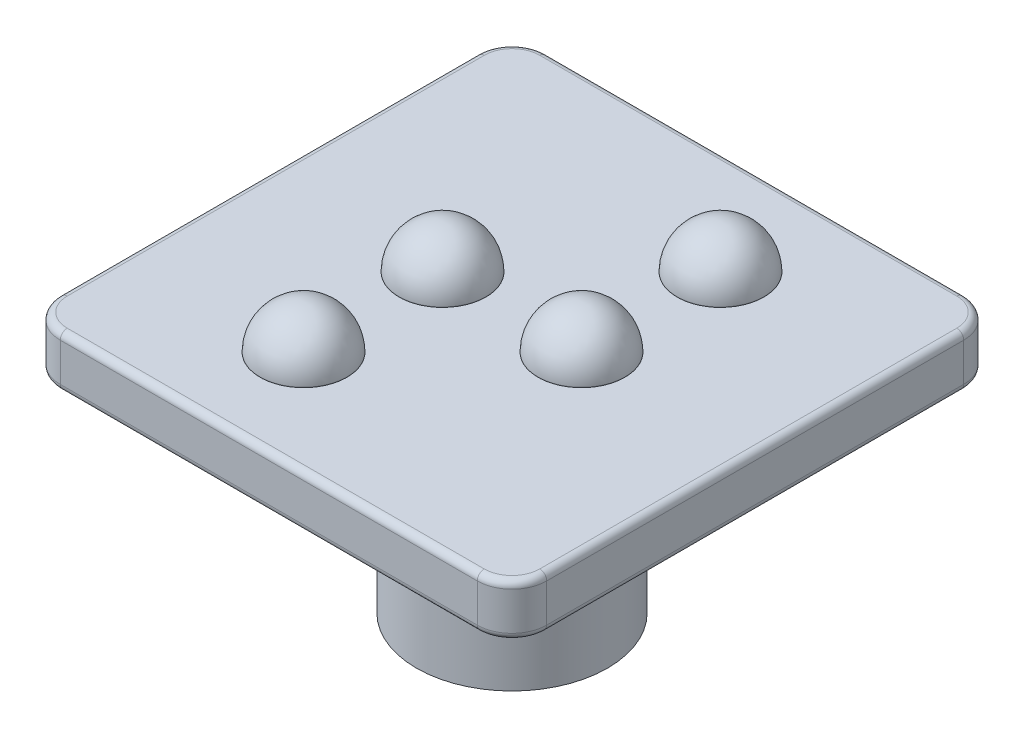
SolidWorks part; units mm, degrees
ref_plane "Front Plane" through (0, 0, 0) normal (0, 0, 1) x (1, 0, 0)
ref_plane "Top Plane" through (0, 0, 0) normal (0, 1, 0) x (1, 0, 0)
ref_plane "Right Plane" through (0, 0, 0) normal (1, 0, 0) x (0, 0, -1)
sketch "Sketch1" plane through (0, 0, 0) normal (0, 1, 0) x (1, 0, 0)
  line L1 (-7.3247, 4.3967) -> (4.6753, 4.3967)
  line L2 (-8.3247, 3.3967) -> (-8.3247, -8.6033)
  line L3 (-7.3247, -9.6033) -> (4.6753, -9.6033)
  line L4 (5.6753, 3.3967) -> (5.6753, -8.6033)
  arc A0 (-8.3247, -8.6033) -> (-7.3247, -9.6033) centre (-7.3247, -8.6033) ccw
  arc A1 (4.6753, -9.6033) -> (5.6753, -8.6033) centre (4.6753, -8.6033) ccw
  arc A2 (4.6753, 4.3967) -> (5.6753, 3.3967) centre (4.6753, 3.3967) cw
  arc A3 (-7.3247, 4.3967) -> (-8.3247, 3.3967) centre (-7.3247, 3.3967) ccw
  point P8 (5.6753, -9.6033)
  point P11 (5.6753, 4.3967)
  point P14 (-8.3247, 4.3967)
  dimension "D3" = 1
  dimension "D1" = 14
  dimension "D2" = 14
extrude "Boss-Extrude1" add sketch "Sketch1" along normal blind 1.5
sketch "Sketch2" plane through (0, 0, 0) normal (0, -1, 0) x (1, 0, 0)
  line L0 (-7.3247, 9.6033) -> (4.6753, 9.6033) construction
  line L1 (5.6753, 8.6033) -> (5.6753, -3.3967) construction
  line L2 (-1.3247, -4.3967) -> (-1.3247, 9.6033) construction
  line L3 (-8.3247, 2.6033) -> (5.6753, 2.6033) construction
  line L4 (-8.3247, -3.3967) -> (-8.3247, 8.6033) construction
  circle A0 centre (-1.3247, 2.6033) radius 2.75
  dimension "D1" = 7
  dimension "D2" = 7
extrude "Boss-Extrude2" add sketch "Sketch2" along normal blind 6
sketch "Sketch3" plane through (0, -6, 0) normal (0, -1, 0) x (1, 0, 0)
  line L0 (-1.3247, 5.3533) -> (-1.3247, -0.1467) construction
  line L1 (-3.3247, 3.1533) -> (0.6753, 3.1533)
  line L2 (-3.3247, 3.1533) -> (-3.3247, 2.0533)
  line L3 (-3.3247, 2.0533) -> (0.6753, 2.0533)
  line L4 (0.6753, 3.1533) -> (0.6753, 2.0533)
  line L5 (-1.8747, 4.6033) -> (-0.7747, 4.6033)
  line L6 (-1.8747, 4.6033) -> (-1.8747, 0.6033)
  line L7 (-1.8747, 0.6033) -> (-0.7747, 0.6033)
  line L8 (-0.7747, 4.6033) -> (-0.7747, 0.6033)
  line L9 (-4.0747, 2.6033) -> (1.4253, 2.6033) construction
  circle A3 centre (-1.3247, 2.6033) radius 2.75 construction
  circle A4 centre (-1.3247, 2.6033) radius 2.75 construction
  dimension "D7" = 0.55
  dimension "D1" = 4
  dimension "D2" = 1.1
  dimension "D3" = 1.1
  dimension "D4" = 4
  dimension "D8" = 0.55
extrude "Cut-Extrude1" cut sketch "Sketch3" against normal blind 6 contours L8 L5 L6 L1 | L1 L8 L3 L4 | L8 L1 L6 L3 | L6 L1 L2 L3 | L8 L3 L6 L7 region at (-2.5997, -6, 2.6033) region at (-1.3247, -6, 3.8783) region at (-1.3247, -6, 2.6033) region at (-0.0497, -6, 2.6033) region at (-1.3247, -6, 1.3283)
chamfer "Chamfer1" distance 0.3 angle 45 12 edges at (-1.3247, -6, 0.6033) (-1.8747, -6, 1.3283) (-2.5997, -6, 2.0533) (-3.3247, -6, 2.6033) (-2.5997, -6, 3.1533) (-0.7747, -6, 1.3283) (-0.0497, -6, 2.0533) (0.6753, -6, 2.6033) (-0.0497, -6, 3.1533) (-0.7747, -6, 3.8783) (-1.3247, -6, 4.6033) (-1.8747, -6, 3.8783)
fillet "Fillet1" radius 1 1 edges at (-1.3247, 0, -0.1467)
sketch "Sketch4" plane through (0, 1.5, 0) normal (0, 1, 0) x (1, 0, 0)
  line L0 (-1.3247, 4.3967) -> (-1.3247, -9.6033) construction
  line L1 (4.6753, 4.3967) -> (-7.3247, 4.3967) construction
  line L2 (-7.3247, -9.6033) -> (4.6753, -9.6033) construction
  line L3 (5.6753, -2.6033) -> (-8.3247, -2.6033) construction
  line L4 (-8.3247, 3.3967) -> (-8.3247, -8.6033) construction
  line L5 (5.6753, -8.6033) -> (5.6753, 3.3967) construction
  line L6 (-3.3247, 4.3967) -> (-3.3247, -9.6033) construction
  line L7 (0.6753, 4.3967) -> (0.6753, -9.6033) construction
  line L8 (-8.3247, 1.3967) -> (5.6753, 1.3967) construction
  line L9 (5.6753, -6.6033) -> (-8.3247, -6.6033) construction
  circle A1 centre (0.6753, -2.6033) radius 1.25
  circle A2 centre (-3.3247, -2.6033) radius 1.25
  circle A3 centre (-3.3247, -6.6033) radius 1.25
  circle A5 centre (0.6753, 1.3967) radius 1.25
  dimension "D1" = 4
  dimension "D2" = 4
  dimension "D3" = 2
  dimension "D4" = 2
extrude "Boss-Extrude3" add sketch "Sketch4" along normal blind 0.01
dome "Dome2" faces to dome 1 distance 1.25 reverse direction no elliptical dome no face at (0.6753, 1.51, -0.1467) parameters "D1"=1.25
dome "Dome3" faces to dome 1 distance 1.25 reverse direction no elliptical dome no face at (-3.3247, 1.51, 3.8533) parameters "D1"=1.25
dome "Dome4" faces to dome 1 distance 1.25 reverse direction no elliptical dome no face at (0.6753, 1.51, 3.8533) parameters "D1"=1.25
dome "Dome5" faces to dome 1 distance 1.25 reverse direction no elliptical dome no face at (-3.3247, 1.51, 7.8533) parameters "D1"=1.25
fillet "Fillet3" radius 0.2 16 edges at (5.3824, 1.5, -4.1038) (5.6753, 1.5, 2.6033) (5.3824, 1.5, 9.3104) (-1.3247, 1.5, 9.6033) (-8.0318, 1.5, 9.3104) (-8.0318, 1.5, -4.1038) (-8.3247, 1.5, 2.6033) (-1.3247, 1.5, -4.3967) (5.3824, 0, 9.3104) (5.6753, 0, 2.6033) (5.3824, 0, -4.1038) (-1.3247, 0, -4.3967) (-8.0318, 0, -4.1038) (-8.3247, 0, 2.6033) (-8.0318, 0, 9.3104) (-1.3247, 0, 9.6033)
